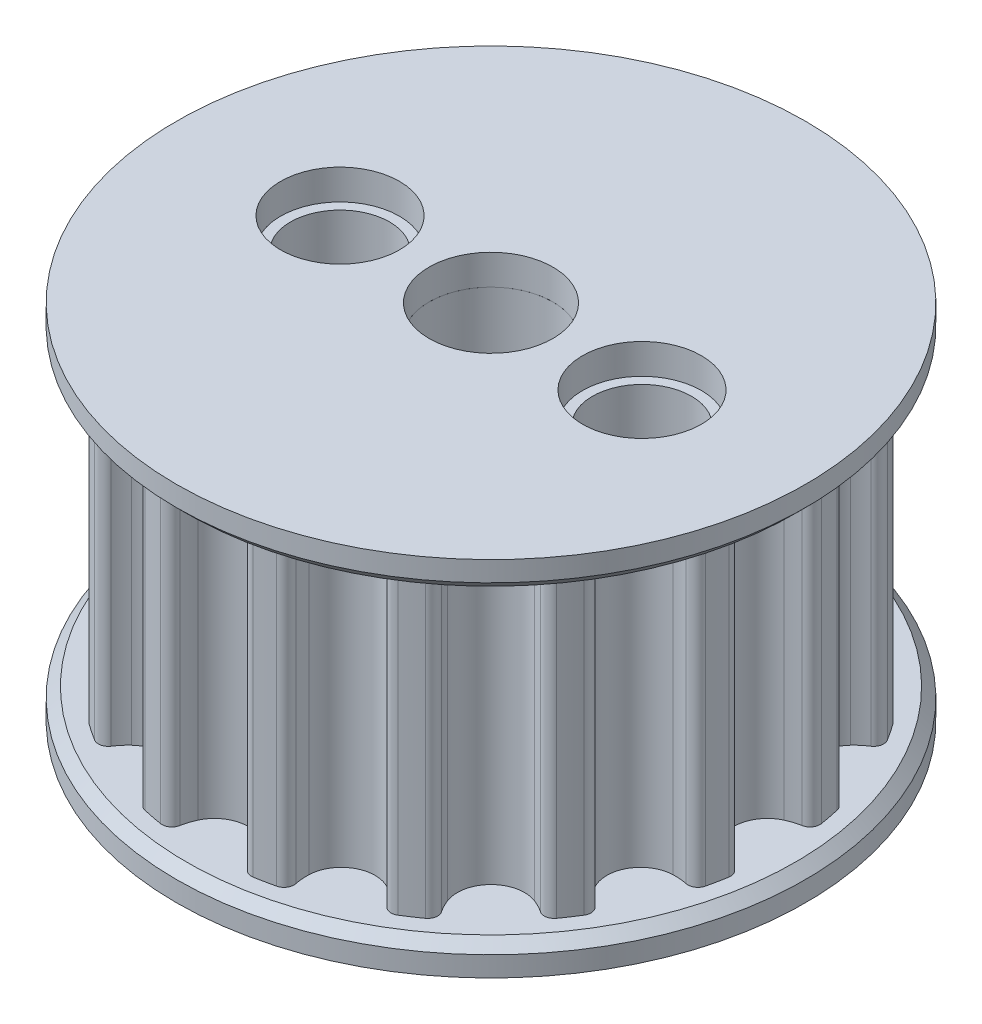
SolidWorks part; units mm, degrees
material "Alum Plate"
ref_plane "Front Plane" through (0, 0, 0) normal (0, 0, 1) x (1, 0, 0)
ref_plane "Top Plane" through (0, 0, 0) normal (0, 1, 0) x (1, 0, 0)
ref_plane "Right Plane" through (0, 0, 0) normal (1, 0, 0) x (0, 0, -1)
other "Bounding Box"
ref_plane "Default Plane" through (-8.9266, -12.7485, 0) normal (-0.1736, 0.9848, 0) x (0.9848, 0.1736, 0)
sketch "Sketch1" plane through (0, 0, 0) normal (0, 1, 0) x (1, 0, 0)
  line L0 (0, -7.8245) -> (0, 0) construction
  circle A0 centre (0, 0) radius 1.5625
  arc B0 (-1.8508, -6.777) -> (-1.6633, -7.0715) centre (-1.6061, -6.8282) ccw
  arc B1 (-1.6633, -7.0715) -> (-1.1695, -7.1697) centre (0, 0) ccw
  arc B2 (-1.1695, -7.1697) -> (-0.8836, -6.9694) centre (-1.1292, -6.923) ccw
  arc B3 (-0.7739, -6.6229) -> (-0.8836, -6.9694) centre (0.61, -7.2516) ccw
  arc B4 (0.7739, -6.6229) -> (-0.7739, -6.6229) centre (0, -6.9745) ccw
  arc B5 (0.8836, -6.9694) -> (0.7739, -6.6229) centre (-0.61, -7.2516) ccw
  arc B6 (0.8836, -6.9694) -> (1.1695, -7.1697) centre (1.1292, -6.923) ccw
  arc B7 (1.1695, -7.1697) -> (1.6633, -7.0715) centre (0, 0) ccw
  arc B8 (1.6633, -7.0715) -> (1.8508, -6.777) centre (1.6061, -6.8282) ccw
  arc B9 (1.8195, -6.4149) -> (1.8508, -6.777) centre (3.3386, -6.4662) ccw
  arc B10 (3.2495, -5.8226) -> (1.8195, -6.4149) centre (2.669, -6.4436) ccw
  arc B11 (3.4834, -6.1008) -> (3.2495, -5.8226) centre (2.2115, -6.9331) ccw
  arc B12 (3.4834, -6.1008) -> (3.8242, -6.1764) centre (3.6926, -5.9639) ccw
  arc B13 (3.8242, -6.1764) -> (4.2428, -5.8967) centre (0, 0) ccw
  arc B14 (4.2428, -5.8967) -> (4.3033, -5.5529) centre (4.0968, -5.6938) ccw
  arc B15 (4.1359, -5.2303) -> (4.3033, -5.5529) centre (5.559, -4.6963) ccw
  arc B16 (5.2303, -4.1359) -> (4.1359, -5.2303) centre (4.9317, -4.9317) ccw
  arc B17 (5.5529, -4.3033) -> (5.2303, -4.1359) centre (4.6963, -5.559) ccw
  arc B18 (5.5529, -4.3033) -> (5.8967, -4.2428) centre (5.6938, -4.0968) ccw
  arc B19 (5.8967, -4.2428) -> (6.1764, -3.8242) centre (0, 0) ccw
  arc B20 (6.1764, -3.8242) -> (6.1008, -3.4834) centre (5.9639, -3.6926) ccw
  arc B21 (5.8226, -3.2495) -> (6.1008, -3.4834) centre (6.9331, -2.2115) ccw
  arc B22 (6.4149, -1.8195) -> (5.8226, -3.2495) centre (6.4436, -2.669) ccw
  arc B23 (6.777, -1.8508) -> (6.4149, -1.8195) centre (6.4662, -3.3386) ccw
  arc B24 (6.777, -1.8508) -> (7.0715, -1.6633) centre (6.8282, -1.6061) ccw
  arc B25 (7.0715, -1.6633) -> (7.1697, -1.1695) centre (0, 0) ccw
  arc B26 (7.1697, -1.1695) -> (6.9694, -0.8836) centre (6.923, -1.1292) ccw
  arc B27 (6.6229, -0.7739) -> (6.9694, -0.8836) centre (7.2516, 0.61) ccw
  arc B28 (6.6229, 0.7739) -> (6.6229, -0.7739) centre (6.9745, 0) ccw
  arc B29 (6.9694, 0.8836) -> (6.6229, 0.7739) centre (7.2516, -0.61) ccw
  arc B30 (6.9694, 0.8836) -> (7.1697, 1.1695) centre (6.923, 1.1292) ccw
  arc B31 (7.1697, 1.1695) -> (7.0715, 1.6633) centre (0, 0) ccw
  arc B32 (7.0715, 1.6633) -> (6.777, 1.8508) centre (6.8282, 1.6061) ccw
  arc B33 (6.4149, 1.8195) -> (6.777, 1.8508) centre (6.4662, 3.3386) ccw
  arc B34 (5.8226, 3.2495) -> (6.4149, 1.8195) centre (6.4436, 2.669) ccw
  arc B35 (6.1008, 3.4834) -> (5.8226, 3.2495) centre (6.9331, 2.2115) ccw
  arc B36 (6.1008, 3.4834) -> (6.1764, 3.8242) centre (5.9639, 3.6926) ccw
  arc B37 (6.1764, 3.8242) -> (5.8967, 4.2428) centre (0, 0) ccw
  arc B38 (5.8967, 4.2428) -> (5.5529, 4.3033) centre (5.6938, 4.0968) ccw
  arc B39 (5.2303, 4.1359) -> (5.5529, 4.3033) centre (4.6963, 5.559) ccw
  arc B40 (4.1359, 5.2303) -> (5.2303, 4.1359) centre (4.9317, 4.9317) ccw
  arc B41 (4.3033, 5.5529) -> (4.1359, 5.2303) centre (5.559, 4.6963) ccw
  arc B42 (4.3033, 5.5529) -> (4.2428, 5.8967) centre (4.0968, 5.6938) ccw
  arc B43 (4.2428, 5.8967) -> (3.8242, 6.1764) centre (0, 0) ccw
  arc B44 (3.8242, 6.1764) -> (3.4834, 6.1008) centre (3.6926, 5.9639) ccw
  arc B45 (3.2495, 5.8226) -> (3.4834, 6.1008) centre (2.2115, 6.9331) ccw
  arc B46 (1.8195, 6.4149) -> (3.2495, 5.8226) centre (2.669, 6.4436) ccw
  arc B47 (1.8508, 6.777) -> (1.8195, 6.4149) centre (3.3386, 6.4662) ccw
  arc B48 (1.8508, 6.777) -> (1.6633, 7.0715) centre (1.6061, 6.8282) ccw
  arc B49 (1.6633, 7.0715) -> (1.1695, 7.1697) centre (0, 0) ccw
  arc B50 (1.1695, 7.1697) -> (0.8836, 6.9694) centre (1.1292, 6.923) ccw
  arc B51 (0.7739, 6.6229) -> (0.8836, 6.9694) centre (-0.61, 7.2516) ccw
  arc B52 (-0.7739, 6.6229) -> (0.7739, 6.6229) centre (0, 6.9745) ccw
  arc B53 (-0.8836, 6.9694) -> (-0.7739, 6.6229) centre (0.61, 7.2516) ccw
  arc B54 (-0.8836, 6.9694) -> (-1.1695, 7.1697) centre (-1.1292, 6.923) ccw
  arc B55 (-1.1695, 7.1697) -> (-1.6633, 7.0715) centre (0, 0) ccw
  arc B56 (-1.6633, 7.0715) -> (-1.8508, 6.777) centre (-1.6061, 6.8282) ccw
  arc B57 (-1.8195, 6.4149) -> (-1.8508, 6.777) centre (-3.3386, 6.4662) ccw
  arc B58 (-3.2495, 5.8226) -> (-1.8195, 6.4149) centre (-2.669, 6.4436) ccw
  arc B59 (-3.4834, 6.1008) -> (-3.2495, 5.8226) centre (-2.2115, 6.9331) ccw
  arc B60 (-3.4834, 6.1008) -> (-3.8242, 6.1764) centre (-3.6926, 5.9639) ccw
  arc B61 (-3.8242, 6.1764) -> (-4.2428, 5.8967) centre (0, 0) ccw
  arc B62 (-4.2428, 5.8967) -> (-4.3033, 5.5529) centre (-4.0968, 5.6938) ccw
  arc B63 (-4.1359, 5.2303) -> (-4.3033, 5.5529) centre (-5.559, 4.6963) ccw
  arc B64 (-5.2303, 4.1359) -> (-4.1359, 5.2303) centre (-4.9317, 4.9317) ccw
  arc B65 (-5.5529, 4.3033) -> (-5.2303, 4.1359) centre (-4.6963, 5.559) ccw
  arc B66 (-5.5529, 4.3033) -> (-5.8967, 4.2428) centre (-5.6938, 4.0968) ccw
  arc B67 (-5.8967, 4.2428) -> (-6.1764, 3.8242) centre (0, 0) ccw
  arc B68 (-6.1764, 3.8242) -> (-6.1008, 3.4834) centre (-5.9639, 3.6926) ccw
  arc B69 (-5.8226, 3.2495) -> (-6.1008, 3.4834) centre (-6.9331, 2.2115) ccw
  arc B70 (-6.4149, 1.8195) -> (-5.8226, 3.2495) centre (-6.4436, 2.669) ccw
  arc B71 (-6.777, 1.8508) -> (-6.4149, 1.8195) centre (-6.4662, 3.3386) ccw
  arc B72 (-6.777, 1.8508) -> (-7.0715, 1.6633) centre (-6.8282, 1.6061) ccw
  arc B73 (-7.0715, 1.6633) -> (-7.1697, 1.1695) centre (0, 0) ccw
  arc B74 (-7.1697, 1.1695) -> (-6.9694, 0.8836) centre (-6.923, 1.1292) ccw
  arc B75 (-6.6229, 0.7739) -> (-6.9694, 0.8836) centre (-7.2516, -0.61) ccw
  arc B76 (-6.6229, -0.7739) -> (-6.6229, 0.7739) centre (-6.9745, 0) ccw
  arc B77 (-6.9694, -0.8836) -> (-6.6229, -0.7739) centre (-7.2516, 0.61) ccw
  arc B78 (-6.9694, -0.8836) -> (-7.1697, -1.1695) centre (-6.923, -1.1292) ccw
  arc B79 (-7.1697, -1.1695) -> (-7.0715, -1.6633) centre (0, 0) ccw
  arc B80 (-7.0715, -1.6633) -> (-6.777, -1.8508) centre (-6.8282, -1.6061) ccw
  arc B81 (-6.4149, -1.8195) -> (-6.777, -1.8508) centre (-6.4662, -3.3386) ccw
  arc B82 (-5.8226, -3.2495) -> (-6.4149, -1.8195) centre (-6.4436, -2.669) ccw
  arc B83 (-6.1008, -3.4834) -> (-5.8226, -3.2495) centre (-6.9331, -2.2115) ccw
  arc B84 (-6.1008, -3.4834) -> (-6.1764, -3.8242) centre (-5.9639, -3.6926) ccw
  arc B85 (-6.1764, -3.8242) -> (-5.8967, -4.2428) centre (0, 0) ccw
  arc B86 (-5.8967, -4.2428) -> (-5.5529, -4.3033) centre (-5.6938, -4.0968) ccw
  arc B87 (-5.2303, -4.1359) -> (-5.5529, -4.3033) centre (-4.6963, -5.559) ccw
  arc B88 (-4.1359, -5.2303) -> (-5.2303, -4.1359) centre (-4.9317, -4.9317) ccw
  arc B89 (-4.3033, -5.5529) -> (-4.1359, -5.2303) centre (-5.559, -4.6963) ccw
  arc B90 (-4.3033, -5.5529) -> (-4.2428, -5.8967) centre (-4.0968, -5.6938) ccw
  arc B91 (-4.2428, -5.8967) -> (-3.8242, -6.1764) centre (0, 0) ccw
  arc B92 (-3.8242, -6.1764) -> (-3.4834, -6.1008) centre (-3.6926, -5.9639) ccw
  arc B93 (-3.2495, -5.8226) -> (-3.4834, -6.1008) centre (-2.2115, -6.9331) ccw
  arc B94 (-1.8195, -6.4149) -> (-3.2495, -5.8226) centre (-2.669, -6.4436) ccw
  arc B95 (-1.8508, -6.777) -> (-1.8195, -6.4149) centre (-3.3386, -6.4662) ccw
  dimension "D1" = 3.125
sketch_block_instance "Block-GT2 16 Tooth Profile-1"
sketch_block "Block-GT2 16 Tooth Profile" parameters "D1"=2.1152
extrude "Boss-Extrude1" add sketch "Sketch1" along normal mid plane 7.62
sketch "Sketch2" plane through (0, -3.81, 0) normal (0, -1, 0) x (1, 0, 0)
  circle A0 centre (0, 0) radius 7.9375
  circle A1 centre (0, 0) radius 1.5625 construction
  circle A2 centre (0, 0) radius 1.5625
  dimension "D1" = 15.875
extrude "Boss-Extrude2" add sketch "Sketch2" along normal blind 0.762 separate body
sketch "Sketch3" plane through (0, -4.572, 0) normal (0, -1, 0) x (1, 0, 0)
  line L0 (0, 0) -> (3.81, 0) construction
  line L1 (0, 0) -> (-3.81, 0) construction
  circle A0 centre (-3.81, 0) radius 1.5
  circle A1 centre (3.81, 0) radius 1.5
  dimension "D1" = 3
  dimension "D2" = 3.81
extrude "Cut-Extrude1" cut sketch "Sketch3" against normal through all
sketch "Sketch4" plane through (0, -3.81, 0) normal (0, -1, 0) x (1, 0, 0)
  circle A0 centre (-3.81, 0) radius 1.25
  circle A1 centre (3.81, 0) radius 1.25
  dimension "D1" = 2.5
extrude "Cut-Extrude2" cut sketch "Sketch4" against normal through all
chamfer "Chamfer1" distance 0.254 angle 45 1 edges at (0, -3.81, -7.9375)
mirror "Mirror2" about plane through (0, 0, 0) normal (0, 1, 0) of bodies 107 105
